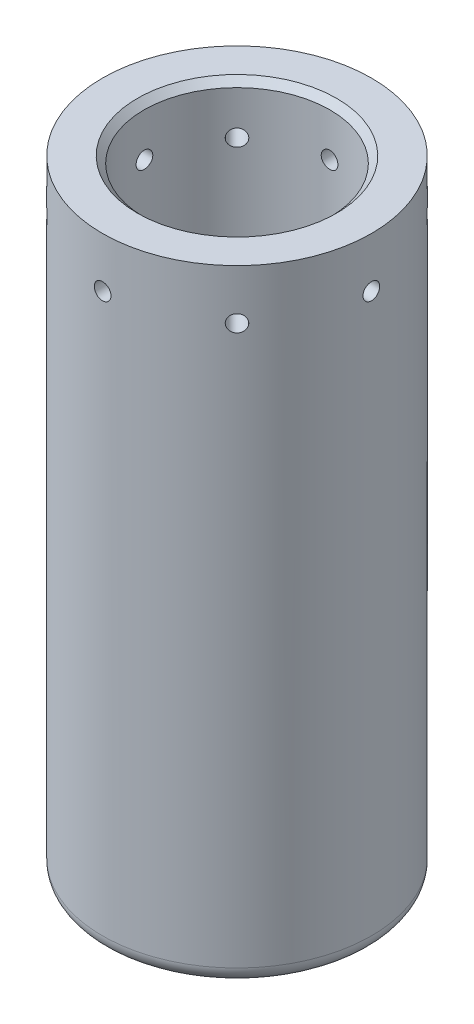
SolidWorks part; units mm, degrees
ref_plane "Front" through (0, 0, 0) normal (0, 0, 1) x (1, 0, 0)
ref_plane "Top" through (0, 0, 0) normal (0, 1, 0) x (1, 0, 0)
ref_plane "Right" through (0, 0, 0) normal (1, 0, 0) x (0, 0, -1)
sketch "Sketch1" plane through (0, 0, 0) normal (0, 1, 0) x (1, 0, 0)
  circle A0 centre (0, 0) radius 16.15
  circle A1 centre (0, 0) radius 11.15
  dimension "D1" = 32.3
  dimension "D2" = 5
extrude "Boss-Extrude1" add sketch "Sketch1" along normal blind 70
sketch "Sketch2" plane through (0, 0, 0) normal (0, -1, 0) x (1, 0, 0)
  circle A1 centre (0, 0) radius 16.15 construction
  circle A2 centre (0, 0) radius 16.15
extrude "Boss-Extrude2" add sketch "Sketch2" along normal blind 5
chamfer "Chamfer1" distance 5 angle 45 1 edges at (0, 0, 11.15)
fillet "Fillet1" radius 2 1 edges at (0, -5, -16.15)
chamfer "Chamfer2" distance 0.8 angle 45 1 edges at (0, 70, 11.15)
ref_plane "Plane1" through (16.15, 0, 0) normal (1, 0, 0) x (0, 0, -1)
sketch "Sketch3" plane through (16.15, 0, 0) normal (1, 0, 0) x (0, 0, -1)
  line L0 (0, 70) -> (0, 51.6689) construction
  line L1 (16.15, 70) -> (-16.15, 70) construction
  circle A0 centre (0, 64) radius 1
  dimension "D1" = 2
  dimension "D2" = 6
extrude "Cut-Extrude1" cut sketch "Sketch3" against normal blind 10
ref_axis "Axis1" through (0, 69.2, 0) along (0, -1, 0)
pattern_circular "CirPattern1" count 8 over 360 about axis through (0, 69.2, 0) along (0, -1, 0) of "Cut-Extrude1"
